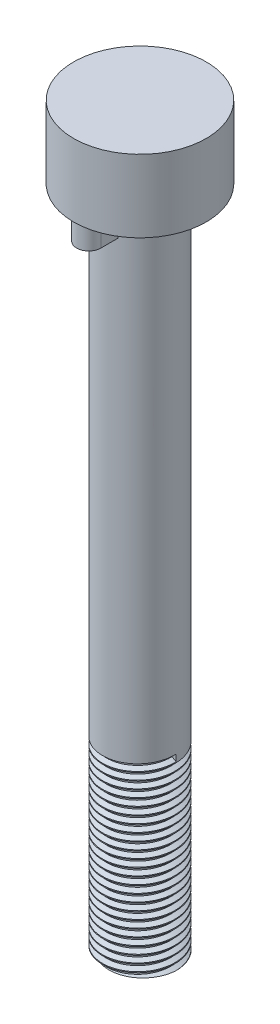
SolidWorks part; units mm, degrees
material "Gray Cast Iron"
ref_plane "Front Plane" through (0, 0, 0) normal (0, 0, 1) x (1, 0, 0)
ref_plane "Top Plane" through (0, 0, 0) normal (0, 1, 0) x (1, 0, 0)
ref_plane "Right Plane" through (0, 0, 0) normal (1, 0, 0) x (0, 0, -1)
sketch "Sketch1" plane through (0, 0, 0) normal (0, 1, 0) x (1, 0, 0)
  line L0 (0, 0) -> (-13627.5891, 0) construction
  line L1 (0, 0) -> (0, -13627.5891) construction
  circle A0 centre (0, 0) radius 6
  circle A1 centre (0, 0) radius 11
  dimension "D1" = 22
  dimension "D2" = 12
extrude "Boss-Extrude1" add sketch "Sketch1" against normal blind 12
extrude "Boss-Extrude2" add sketch "Sketch1<3>" against normal blind 122 contours A0 region at (0, 0, 0)
sketch "Sketch1<3>" plane through (0, 0, 0) normal (0, 1, 0) x (1, 0, 0) same geometry as "Sketch1"
sketch "Sketch2" plane through (0, -12, 0) normal (0, -1, 0) x (1, 0, 0)
  line L0 (0, 0) -> (-50000, 0) construction
  line L1 (0, 0) -> (0, -50000) construction
  line L2 (2, 8.5) -> (2, 5.6569)
  line L3 (-2, 8.5) -> (-2, 5.6569)
  arc A1 (2, 8.5) -> (-2, 8.5) centre (0, 8.5) ccw
  circle A2 centre (0, 0) radius 6 construction
  arc A3 (2, 5.6569) -> (-2, 5.6569) centre (0, 0) ccw
  dimension "D1" = 4
  dimension "D2" = 8.5
extrude "Boss-Extrude3" add sketch "Sketch2" along normal blind 4
thread "Thread1" pitch 1.25 method cut profile "Thread Profile1" start angle 0, offset 5, length 35, pitch 1.25, diameter 12
ref_plane "Plane1" through (6, -127, 0) normal (0, 0, 1) x (1, 0, 0)
sketch "Thread Profile1" plane through (6, -127, 0) normal (0, 0, 1) x (1, 0, 0)
  line L0 (0, 0) -> (0, 1.25) construction
  line L11 (0, 0) -> (0, 1.0937)
  line L12 (0, 1.0937) -> (-0.6766, 0.7031)
  line L13 (-0.6766, 0.7031) -> (-0.6766, 0.3906)
  line L15 (-0.6766, 0.3906) -> (0, 0)
  line L17 (-0.6766, 0.5469) -> (0, 0.5469) construction
  point P2 (0, 0)
  dimension "Pitch" = 1.25
  dimension "Profile_Angle" = 60
  dimension "Profile_Land" = 0.3125
  dimension "Profile_Height" = 0.6766
